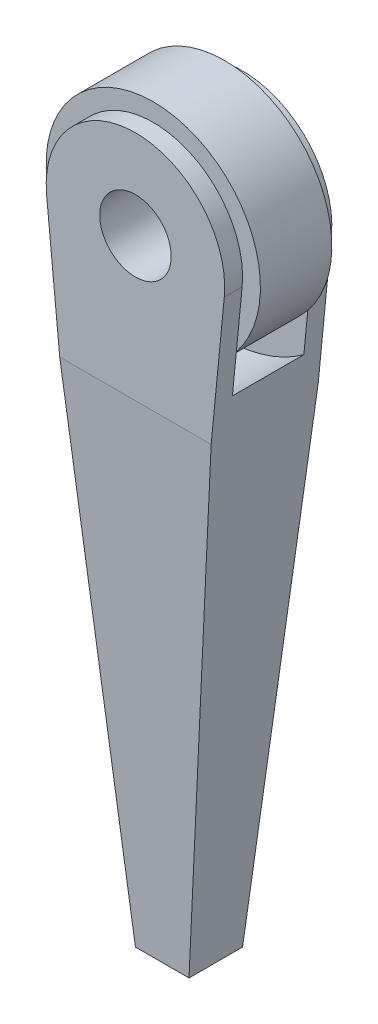
SolidWorks part; units mm, degrees
ref_plane "Front Plane" through (0, 0, 0) normal (0, 0, 1) x (1, 0, 0)
ref_plane "Top Plane" through (0, 0, 0) normal (0, 1, 0) x (1, 0, 0)
ref_plane "Right Plane" through (0, 0, 0) normal (1, 0, 0) x (0, 0, -1)
sketch "Sketch1" plane through (0, 0, 0) normal (0, 0, 1) x (1, 0, 0)
  line L0 (-1000, 0) -> (49000, 0) construction
  line L1 (0, -1001.1589) -> (0, 48998.8411) construction
  line L2 (-1000, -180) -> (49000, -180) construction
  line L3 (24.8811, -2.4355) -> (7.5, -180)
  line L4 (-7.5, -180) -> (7.5, -180)
  line L5 (-7.5, -180) -> (-24.8811, -2.4355)
  circle A0 centre (0, 0) radius 10
  circle A2 centre (0, 0) radius 30
  circle A3 centre (0, 0) radius 25
  circle A4 centre (0, 0) radius 37.5
  point P13 (0, 0)
  point P15 (0, 0)
  point P17 (0, -180)
  dimension "D1" = 20
  dimension "D2" = 180
  dimension "D3" = 60
  dimension "D4" = 15
  dimension "D5" = 50
  dimension "D6" = 75
extrude "Boss-Extrude1" add sketch "Sketch1" along normal mid plane 30 contours A2 A0 | A2 L5 L3 | A3 L5 A2 L3 | A4 L5 L4 L3 region at (23.5072, -10.6322, 0) region at (0, -24.2929, 0) region at (0, -30.6484, 0) region at (0, -95.8779, 0)
extrude "Cut-Extrude1" cut sketch "Sketch1<4>" against normal mid plane 20 contours L5 A4 L3 A2 | A3 L5 A2 L3 region at (23.5072, -10.6322, 0) region at (0, -30.6484, 0)
sketch "Sketch1<4>" plane through (0, 0, 0) normal (0, 0, 1) x (1, 0, 0) same geometry as "Sketch1"
extrude "Boss-Extrude2" add sketch "Sketch1<5>" along normal mid plane 20 contours A3 L3 A2 L5 | A3 L5 A2 L3 region at (25.7436, -1.257, 0) region at (23.5072, -10.6322, 0)
sketch "Sketch1<5>" plane through (0, 0, 0) normal (0, 0, 1) x (1, 0, 0) same geometry as "Sketch1"
sketch "Sketch3" plane through (0, 0, 0) normal (1, 0, 0) x (0, 0, -1)
  line L0 (-1000, 0) -> (49000, 0) construction
  line L1 (0, -1000) -> (0, 49000) construction
  line L2 (-1000, -40) -> (49000, -40) construction
  line L3 (-7.5, -180) -> (7.5, -180)
  line L4 (-15, -180) -> (15, -180) construction
  line L5 (-15, -40) -> (15, -40)
  line L6 (-15, -2.4355) -> (-15, -180) construction
  line L7 (15, -2.4355) -> (15, -180) construction
  line L8 (15, -40) -> (7.5, -180)
  line L9 (-15, -40) -> (-7.5, -180)
  line L20 (15, -2.4355) -> (10, -2.4355)
  line L21 (10, -2.4355) -> (10, -18.9398)
  line L22 (10, -18.9398) -> (10, -30.2534)
  line L23 (10, -30.2534) -> (-10, -30.2534)
  line L24 (-10, -30.2534) -> (-10, -18.9398)
  line L25 (-10, -18.9398) -> (-10, -2.4355)
  line L26 (-10, -2.4355) -> (-15, -2.4355)
  line L27 (-15, -2.4355) -> (-15, -180)
  line L28 (-15, -180) -> (15, -180)
  line L29 (15, -180) -> (15, -2.4355)
  line L37 (-15, -40) -> (-15, -180)
  line L38 (-15, -180) -> (15, -180)
  line L39 (15, -180) -> (15, -40)
  point P12 (0, -180)
  dimension "D1" = 40
  dimension "D2" = 15
  dimension "D3" = 0
extrude "Cut-Extrude2" cut sketch "Sketch3" against normal through all both and the other way through all contours L37 L38 L9 | L38 L39 L8 region at (0, -133.3333, 12.5) region at (0, -133.3333, -12.5)
